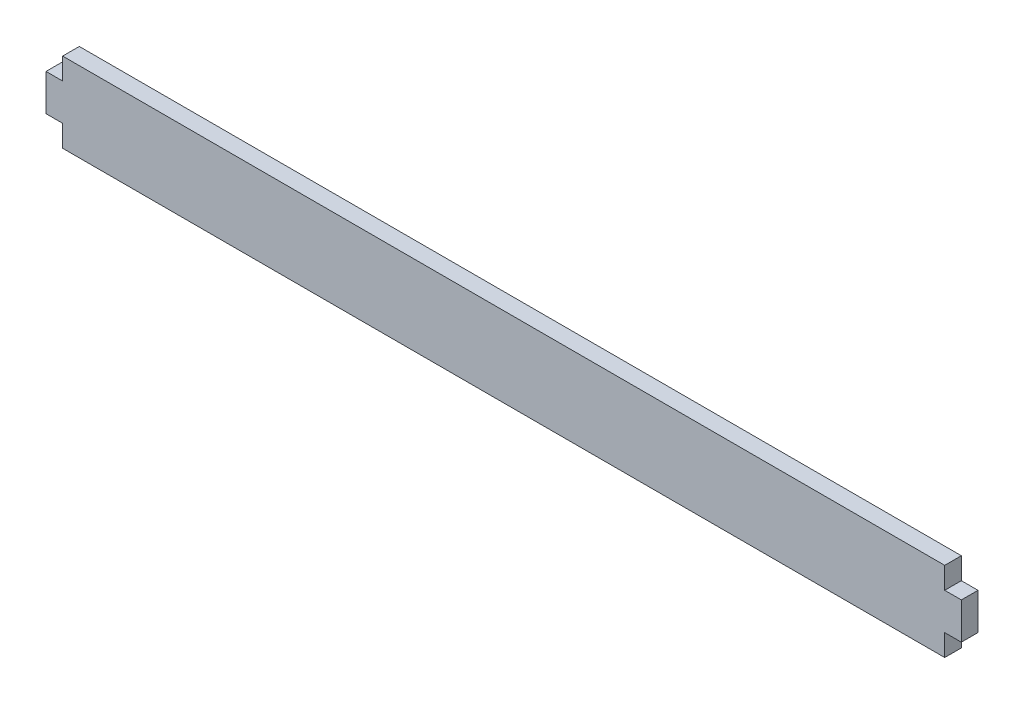
SolidWorks part; units mm, degrees
material "Фанера березовая"
ref_plane "Front Plane" through (0, 0, 0) normal (0, 0, 1) x (1, 0, 0)
ref_plane "Top Plane" through (0, 0, 0) normal (0, 1, 0) x (1, 0, 0)
ref_plane "Right Plane" through (0, 0, 0) normal (1, 0, 0) x (0, 0, -1)
sketch "Sketch1" plane through (0, 0, 0) normal (0, 0, 1) x (1, 0, 0)
  line L1 (-275, 24) -> (275, 24)
  line L2 (-275, 24) -> (-275, -24)
  line L3 (-275, -24) -> (275, -24)
  line L4 (275, 24) -> (275, -24)
  line L5 (-275, 24) -> (275, -24) construction
  line L6 (-275, -24) -> (275, 24) construction
  point P0 (0, 0)
  dimension "D1" = 550
  dimension "D2" = 48
extrude "Основа" add sketch "Sketch1" along normal blind 10
sketch "Sketch2" plane through (0, 0, 10) normal (0, 0, 1) x (1, 0, 0)
  line L0 (-275, -11) -> (-265, -11)
  line L1 (-275, 24) -> (-275, -24) construction
  line L2 (-265, -11) -> (-265, 11) construction
  line L3 (-265, 11) -> (-275, 11)
  line L4 (-275, 11) -> (-275, -11) construction
  line L5 (0, 24) -> (0, -24) construction
  line L6 (275, 24) -> (-275, 24) construction
  line L7 (-275, -24) -> (275, -24) construction
  line L8 (-275, -11) -> (-275, -24)
  line L9 (-275, -24) -> (-265, -24)
  line L10 (-265, -24) -> (-265, -11)
  line L11 (-275, 24) -> (-275, 11)
  line L12 (-265, 11) -> (-265, 24)
  line L13 (-265, 24) -> (-275, 24)
  point P13 (-275, 0)
  point P14 (-275, 0)
  dimension "D1" = 10
  dimension "D2" = 22
extrude "Шип" cut sketch "Sketch2" against normal up to next
sketch "Sketch3" plane through (0, 0, 10) normal (0, 0, 1) x (1, 0, 0)
  line L3 (-275, 11) -> (-265, 11) construction
  line L4 (-275, 11) -> (-275, -11) construction
  circle A2 centre (-270, 0) radius 1.5
  point P5 (-270, 11)
  point P9 (-275, 0)
  dimension "D1" = 3
extrude "Крепежные" [suppressed] cut sketch "Sketch3" against normal up to next
mirror "Mirror1" about plane through (0, 0, 0) normal (1, 0, 0) of "Крепежные", "Шип"
